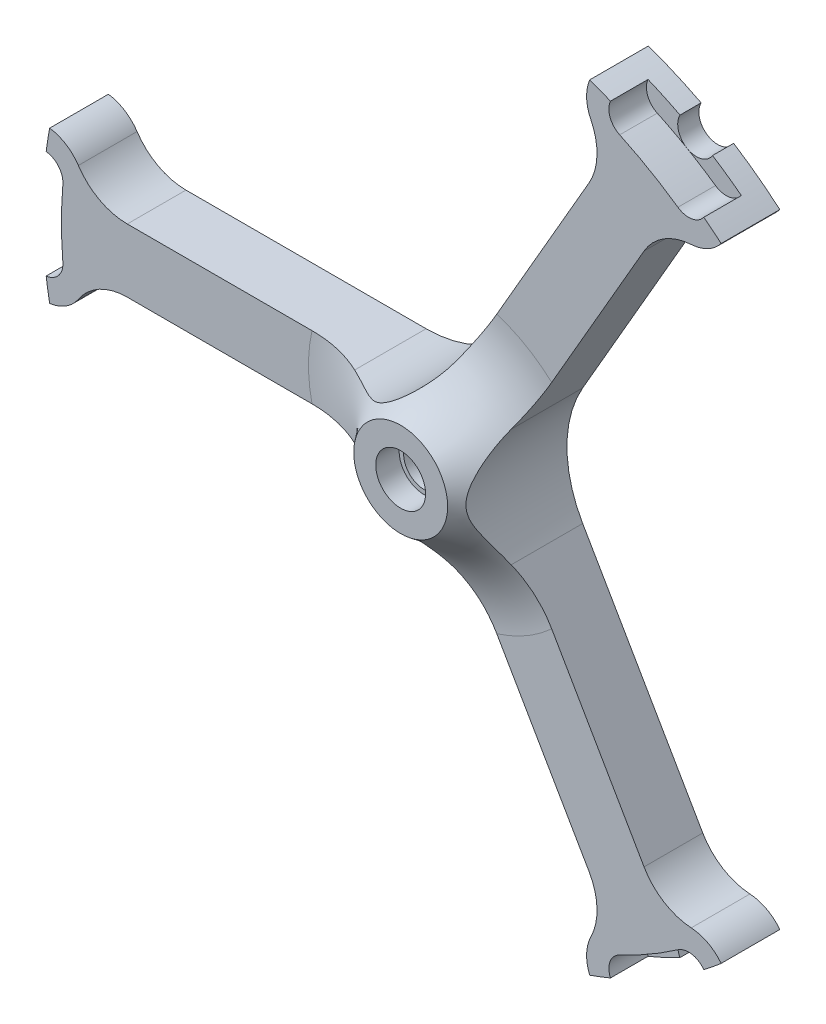
SolidWorks part; units mm, degrees
ref_plane "Plan de face" through (0, 0, 0) normal (0, 0, 1) x (1, 0, 0)
ref_plane "Plan de dessus" through (0, 0, 0) normal (0, 1, 0) x (1, 0, 0)
ref_plane "Plan de droite" through (0, 0, 0) normal (1, 0, 0) x (0, 0, -1)
sketch "Esquisse1" plane through (0, 0, 0) normal (0, 0, 1) x (1, 0, 0)
  line L19 (-1000, 0) -> (49000, 0) construction
  line L21 (-27.7888, 2.7) -> (-7.3323, 2.7)
  line L23 (-27.7888, -2.7) -> (-7.3323, -2.7)
  line L33 (16.2327, 22.7158) -> (6.0044, 5)
  line L34 (11.5561, 25.4158) -> (1.3279, 7.7)
  line L35 (11.5561, -25.4158) -> (1.3279, -7.7)
  line L36 (16.2327, -22.7158) -> (6.0044, -5)
  arc A0 (-34.3972, 6.4678) -> (-34.6976, 4.5906) centre (0, 0) ccw
  arc A7 (-33.2771, 2.8629) -> (-34.6976, 4.5906) centre (-34.8712, 3) ccw
  arc A8 (-33.2771, -2.8629) -> (-34.6976, -4.5906) centre (-34.8712, -3) cw
  arc A12 (-33.2771, 2.8629) -> (-33.2771, -2.8629) centre (0, 0) ccw
  arc A13 (-31.9549, 4.9353) -> (-34.3972, 6.4678) centre (-34.8712, 3) ccw
  arc A14 (-31.9549, -4.9353) -> (-34.3972, -6.4678) centre (-34.8712, -3) cw
  arc A15 (-34.6976, -4.5906) -> (-34.3972, -6.4678) centre (0, 0) ccw
  arc A16 (-27.7888, -2.7) -> (-31.9549, -4.9353) centre (-27.7888, -7.7) ccw
  arc A17 (-27.7888, 2.7) -> (-31.9549, 4.9353) centre (-27.7888, 7.7) cw
  arc A48 (22.7998, 26.555) -> (21.3244, 27.7538) centre (0, 0) ccw
  arc A49 (19.1178, 27.3874) -> (21.3244, 27.7538) centre (20.0337, 28.6993) ccw
  arc A50 (14.1592, 30.2502) -> (13.3733, 32.3443) centre (14.8375, 31.6993) cw
  arc A51 (19.1178, 27.3874) -> (14.1592, 30.2502) centre (0, 0) ccw
  arc A52 (20.2516, 25.2061) -> (22.7998, 26.555) centre (20.0337, 28.6993) ccw
  arc A53 (11.7034, 30.1414) -> (11.5974, 33.0227) centre (14.8375, 31.6993) cw
  arc A54 (13.3733, 32.3443) -> (11.5974, 33.0227) centre (0, 0) ccw
  arc A55 (11.5561, 25.4158) -> (11.7034, 30.1414) centre (7.226, 27.9158) ccw
  arc A56 (16.2327, 22.7158) -> (20.2516, 25.2061) centre (20.5628, 20.2158) cw
  arc A57 (11.5974, -33.0227) -> (13.3733, -32.3443) centre (0, 0) ccw
  arc A58 (14.1592, -30.2502) -> (13.3733, -32.3443) centre (14.8375, -31.6993) ccw
  arc A59 (19.1178, -27.3874) -> (21.3244, -27.7538) centre (20.0337, -28.6993) cw
  arc A60 (14.1592, -30.2502) -> (19.1178, -27.3874) centre (0, 0) ccw
  arc A61 (11.7034, -30.1414) -> (11.5974, -33.0227) centre (14.8375, -31.6993) ccw
  arc A62 (20.2516, -25.2061) -> (22.7998, -26.555) centre (20.0337, -28.6993) cw
  arc A63 (21.3244, -27.7538) -> (22.7998, -26.555) centre (0, 0) ccw
  arc A64 (16.2327, -22.7158) -> (20.2516, -25.2061) centre (20.5628, -20.2158) ccw
  arc A65 (11.5561, -25.4158) -> (11.7034, -30.1414) centre (7.226, -27.9158) cw
  arc A66 (-7.3323, -2.7) -> (1.3279, -7.7) centre (-7.3323, -12.7) cw
  arc A67 (6.0044, -5) -> (6.0044, 5) centre (14.6647, 0) cw
  arc A68 (1.3279, 7.7) -> (-7.3323, 2.7) centre (-7.3323, 12.7) cw
  point P38 (0, 0)
  point P50 (3.1177, 0)
  point P55 (0, 0)
  point P56 (0, 0)
  point P80 (0, 0)
  dimension "D1" = 70
  dimension "D3" = 3
  dimension "D2" = 3.2
  dimension "D4" = 5
  dimension "D5" = 10
extrude "Boss.-Extru.1" add sketch "Esquisse1" along normal blind 5
sketch "Esquisse7" plane through (0, 0, 0) normal (0, 0, -1) x (-1, 0, 0)
  line L0 (-1000, 0) -> (49000, 0) construction
  arc A0 (34.6976, -4.5906) -> (34.6976, 4.5906) centre (0, 0) ccw
  arc A2 (33.2771, -2.8629) -> (33.2771, 2.8629) centre (0, 0) ccw
  arc A4 (34.9634, 1.5996) -> (34.9634, -1.5996) centre (35, 0) ccw
  arc A5 (34.6976, 4.5906) -> (33.2771, 2.8629) centre (34.8712, 3) ccw
  arc A6 (33.2771, -2.8629) -> (33.2771, 2.8629) centre (0, 0) ccw construction
  arc A7 (34.6976, -4.5906) -> (33.2771, -2.8629) centre (34.8712, -3) cw
  arc A8 (-21.3244, -27.7538) -> (-13.3733, -32.3443) centre (0, 0) ccw
  arc A9 (-19.1178, -27.3874) -> (-14.1592, -30.2502) centre (0, 0) ccw
  arc A10 (-16.0964, -31.079) -> (-18.867, -29.4794) centre (-17.5, -30.3109) ccw
  arc A11 (-13.3733, -32.3443) -> (-14.1592, -30.2502) centre (-14.8375, -31.6993) ccw
  arc A12 (-21.3244, -27.7538) -> (-19.1178, -27.3874) centre (-20.0337, -28.6993) cw
  arc A13 (-13.3733, 32.3443) -> (-21.3244, 27.7538) centre (0, 0) ccw
  arc A14 (-14.1592, 30.2502) -> (-19.1178, 27.3874) centre (0, 0) ccw
  arc A15 (-18.867, 29.4794) -> (-16.0964, 31.079) centre (-17.5, 30.3109) ccw
  arc A16 (-21.3244, 27.7538) -> (-19.1178, 27.3874) centre (-20.0337, 28.6993) ccw
  arc A17 (-13.3733, 32.3443) -> (-14.1592, 30.2502) centre (-14.8375, 31.6993) cw
  point P36 (0, 0)
  arc M44 (34.6976, -4.5906) -> (33.2771, -2.8629) centre (34.8712, -3) cw
  arc M45 (33.2771, -2.8629) -> (33.2771, 2.8629) centre (0, 0) ccw
  arc M46 (33.2771, 2.8629) -> (34.6976, 4.5906) centre (34.8712, 3) cw
  arc M56 (-13.3733, 32.3443) -> (-14.1592, 30.2502) centre (-14.8375, 31.6993) cw
  arc M57 (-14.1592, 30.2502) -> (-19.1178, 27.3874) centre (0, 0) ccw
  arc M58 (-19.1178, 27.3874) -> (-21.3244, 27.7538) centre (-20.0337, 28.6993) cw
  arc M68 (-21.3244, -27.7538) -> (-19.1178, -27.3874) centre (-20.0337, -28.6993) cw
  arc M69 (-19.1178, -27.3874) -> (-14.1592, -30.2502) centre (0, 0) ccw
  arc M70 (-14.1592, -30.2502) -> (-13.3733, -32.3443) centre (-14.8375, -31.6993) cw
  dimension "D1" = 3.2
  dimension "D3" = 3.2
  dimension "D4" = 70
  dimension "D2" = 3
extrude "Boss.-Extru.5" add sketch "Esquisse7" against normal blind 1.8 contours A4 A0 A2 M46 | A4 A0 M45 M44 | A10 A8 A9 M70 | A10 A8 M69 M68 | A15 A13 M57 M56 | A15 A13 A14 M58 region at (-34.0862, -2.7129, 0) region at (-34.0862, 2.7129, 0) region at (19.3926, -28.1631, 0) region at (14.6937, -30.876, 0) region at (14.6937, 30.876, 0) region at (19.3926, 28.1631, 0)
sketch "Esquisse4" plane through (0, 0, 5) normal (0, 0, 1) x (1, 0, 0)
  circle A1 centre (0, 0) radius 4
  dimension "D1" = 8
extrude "Boss.-Extru.3" add sketch "Esquisse4" along normal blind 4.5
sketch "Esquisse5" plane through (0, 0, 9.5) normal (0, 0, 1) x (1, 0, 0)
  circle A0 centre (0, 0) radius 2.125
  dimension "D1" = 4.25
extrude "Enlèv. mat.-Extru.2" cut sketch "Esquisse5" against normal blind 2
fillet "Congé1" radius 10 1 edges at (4, 0, 5)
sketch "Esquisse6" plane through (0, 0, 7.5) normal (0, 0, 1) x (1, 0, 0)
  circle A0 centre (0, 0) radius 1.75
  dimension "D1" = 3.5
extrude "Enlèv. mat.-Extru.3" cut sketch "Esquisse6" against normal up to next
